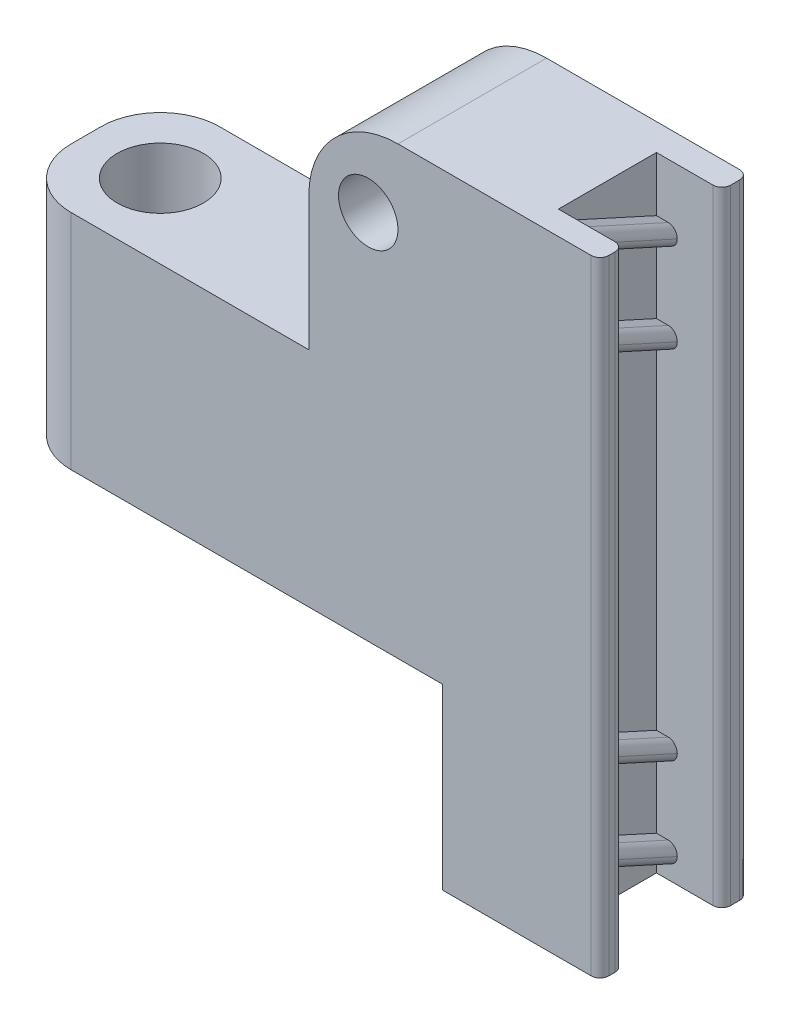
SolidWorks part; units mm, degrees
ref_plane "前基準面" through (0, 0, 0) normal (0, 0, 1) x (1, 0, 0)
ref_plane "上基準面" through (0, 0, 0) normal (0, 1, 0) x (1, 0, 0)
ref_plane "右基準面" through (0, 0, 0) normal (1, 0, 0) x (0, 0, -1)
sketch "草圖1" plane through (0, 0, 0) normal (0, 1, 0) x (1, 0, 0)
  line L0 (17.3, -0.9) -> (14.5, -0.9)
  line L1 (0, 0) -> (17.3, 0)
  line L3 (0, -5) -> (17.3, -5)
  line L4 (17.3, 0) -> (17.3, -0.9)
  line L5 (14.5, -0.9) -> (14.5, -4.2)
  line L6 (14.5, -4.2) -> (17.3, -4.2)
  line L7 (17.3, -4.2) -> (17.3, -5)
  line L9 (0, 0) -> (0, -5) construction
  line L10 (0, 0) -> (-2.5, 0)
  line L11 (-2.5, 0) -> (-2.5, -5)
  line L12 (-2.5, -5) -> (0, -5)
  circle A1 centre (0, -2.5) radius 1.45
  dimension "D2" = 2.5
  dimension "D7" = 2.9
  dimension "D1" = 5
  dimension "D3" = 17.3
  dimension "D4" = 0.9
  dimension "D5" = 0.8
  dimension "D6" = 14.5
extrude "填料-伸長1" add sketch "草圖1" along normal blind 21
sketch "草圖2" plane through (14.5, 0, 0) normal (1, 0, 0) x (0, 0, -1)
  line L0 (-4.2, 5.6591) -> (-0.9, 4.1591)
  line L2 (-0.9, 21) -> (-0.9, 0) construction
  line L3 (-0.9, 4.1591) -> (-0.9, 3.5)
  line L5 (-0.9, 3.5) -> (-4.2, 5)
  line L6 (-4.2, 5) -> (-4.2, 5.6591)
  line L7 (-4.2, 2.6591) -> (-0.9, 1.1591)
  line L8 (-4.2, 21) -> (-4.2, 0) construction
  line L9 (-0.9, 1.1591) -> (-0.9, 0.5)
  line L10 (-0.9, 0.5) -> (-4.2, 2)
  line L11 (-4.2, 2) -> (-4.2, 2.6591)
  line L24 (-4.2, 17.6591) -> (-0.9, 16.1591)
  line L25 (-0.9, 16.1591) -> (-0.9, 15.5)
  line L26 (-0.9, 15.5) -> (-4.2, 17)
  line L27 (-4.2, 17) -> (-4.2, 17.6591)
  line L28 (-4.2, 20.6591) -> (-0.9, 19.1591)
  line L29 (-0.9, 19.1591) -> (-0.9, 18.5)
  line L30 (-0.9, 18.5) -> (-4.2, 20)
  line L31 (-4.2, 20) -> (-4.2, 20.6591)
  line L32 (-4.2, 14.6591) -> (-0.9, 13.1591) [skipped]
  line L33 (-0.9, 13.1591) -> (-0.9, 12.5) [skipped]
  line L34 (-0.9, 12.5) -> (-4.2, 14) [skipped]
  line L35 (-4.2, 14) -> (-4.2, 14.6591) [skipped]
  line L36 (-4.2, 8.6591) -> (-0.9, 7.1591) [skipped]
  line L37 (-0.9, 7.1591) -> (-0.9, 6.5) [skipped]
  line L38 (-0.9, 6.5) -> (-4.2, 8) [skipped]
  line L39 (-4.2, 8) -> (-4.2, 8.6591) [skipped]
  line L40 (-4.2, 11.6591) -> (-0.9, 10.1591) [skipped]
  line L41 (-0.9, 10.1591) -> (-0.9, 9.5) [skipped]
  line L42 (-0.9, 9.5) -> (-4.2, 11) [skipped]
  line L43 (-4.2, 11) -> (-4.2, 11.6591) [skipped]
  dimension "D1" = 0.6
  dimension "D2" = 7
  dimension "D4" = 0.5
  dimension "D5" = 1.5
extrude "填料-伸長2" add sketch "草圖2" along normal blind 1.3
fillet "圓角1" radius 0.3 8 edges at (15.8, 1.9091, 2.55) (15.8, 1.25, 2.55) (15.8, 4.25, 2.55) (15.8, 4.9091, 2.55) (15.8, 16.25, 2.55) (15.8, 16.9091, 2.55) (15.8, 19.25, 2.55) (15.8, 19.9091, 2.55)
fillet "圓角2" radius 0.3 4 edges at (17.3, 10.5, 5) (17.3, 10.5, 0) (17.3, 10.5, 0.9) (17.3, 10.5, 4.2)
sketch "草圖3" plane through (0, 0, 0) normal (0, 0, 1) x (1, 0, 0)
  line L0 (-2.5, 21) -> (17, 21) construction
  line L2 (-2.5, 21) -> (-2.5, 0) construction
  circle A1 centre (9.5, 18.5) radius 1
  dimension "D4" = 2
  dimension "D1" = 2.5
  dimension "D2" = 12
extrude "除料-伸長3" cut sketch "草圖3" along normal blind 10
fillet "圓角3" radius 2 2 edges at (-2.5, 10.5, 5) (-2.5, 10.5, 0)
sketch "草圖4" plane through (14.5, 0, 0) normal (1, 0, 0) x (0, 0, -1)
  line L1 (-4.2, 21) -> (-0.9, 21)
  line L2 (-4.2, 21) -> (-4.2, 0)
  line L3 (-4.2, 0) -> (-0.9, 0)
  line L4 (-0.9, 21) -> (-0.9, 0)
extrude "填料-伸長4" add sketch "草圖4" along normal blind 0.6
ref_axis "基準軸1" through (0, 21, 2.5) along (0, -1, 0)
sketch "草圖5" plane through (0, 0, 0) normal (0, 0, 1) x (1, 0, 0)
  line L0 (12, 13.7707) -> (12, -0.7532) construction
  line L1 (0, 21) -> (0, 0) construction
  dimension "D1" = 12
sketch "草圖6" plane through (0, 21, 0) normal (0, 1, 0) x (1, 0, 0)
  line L0 (0, -2.5) -> (16.7, -2.5) construction
  line L2 (14.499, -0.1435) -> (16, -0.1435)
  line L3 (16, -0.1435) -> (16, -0.6265)
  line L4 (16, -4.3735) -> (16, -4.6222)
  line L5 (14.499, -0.1435) -> (14.499, -4.6222)
  line L6 (14.499, -4.6222) -> (16, -4.6222)
  line L7 (15.1, -0.9) -> (15.1, -4.2) construction
  arc A0 (16, -0.6265) -> (16, -4.3735) centre (16.7, -2.5) ccw
  dimension "D2" = 0.9
  dimension "D1" = 2
sketch "草圖7" plane through (0, 0, 5) normal (0, 0, 1) x (1, 0, 0)
  line L0 (0, 21) -> (0, 0) construction
  line L1 (-3, 6) -> (12, 6)
  line L2 (-3, 6) -> (-3, -7.5365)
  line L3 (-3, -7.5365) -> (12, -7.5365)
  line L4 (12, 6) -> (12, -7.5365)
  line L5 (-0.5, 21) -> (17, 21) construction
  line L6 (-0.5, 21) -> (17, 21) construction
  line L7 (-3, 23) -> (7.5, 23)
  line L8 (-3, 23) -> (-3, 13.5)
  line L9 (-3, 13.5) -> (7.5, 13.5)
  line L10 (7.5, 23) -> (7.5, 13.5)
  circle A0 centre (9.5, 18.5) radius 1 construction
  dimension "D4" = 2
  dimension "D1" = 12
  dimension "D2" = 15
  dimension "D3" = 15
  dimension "D5" = 2
  dimension "D6" = 7.5
extrude "除料-伸長4" cut sketch "草圖7" against normal blind 10
fillet "圓角7" radius 3 1 edges at (7.5, 21, 2.5)
